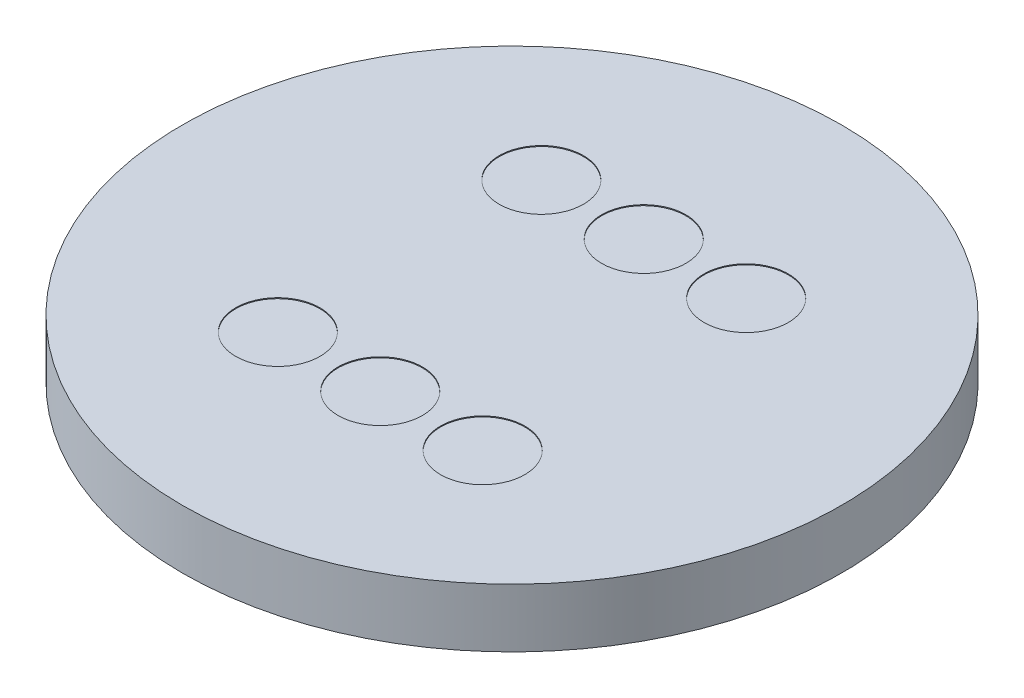
SolidWorks part; units mm, degrees
ref_plane "Front Plane" through (0, 0, 0) normal (0, 0, 1) x (1, 0, 0)
ref_plane "Top Plane" through (0, 0, 0) normal (0, 1, 0) x (1, 0, 0)
ref_plane "Right Plane" through (0, 0, 0) normal (1, 0, 0) x (0, 0, -1)
sketch "Sketch2" plane through (0, 0, 0) normal (0, 1, 0) x (1, 0, 0)
  circle A0 centre (0, 0) radius 9.271
  circle A1 centre (0, 0) radius 7.874
  circle A2 centre (0, 0) radius 5.1435
  circle A3 centre (0, 0) radius 4.826
  circle A4 centre (0, 0) radius 2.159
  circle A5 centre (0, 0) radius 1.905
  dimension "D1" = 18.542
  dimension "D2" = 15.748
  dimension "D3" = 10.287
  dimension "D4" = 9.652
  dimension "D5" = 4.318
  dimension "D6" = 3.81
extrude "Boss-Extrude1" add sketch "Sketch2" along normal blind 1.651 contours A0
extrude "Cut-Extrude1" cut sketch "Sketch2<3>" along normal blind 0.0254 contours A1 A2 | A3 A4 | A5 region at (-7.6513, 0, 0) region at (-4.6895, 0, 0) region at (0, 0, 0)
sketch "Sketch2<3>" plane through (0, 0, 0) normal (0, 1, 0) x (1, 0, 0) same geometry as "Sketch2"
sketch "Sketch3" plane through (0, 1.651, 0) normal (0, 1, 0) x (1, 0, 0)
  line L0 (2.8811, -3.7064) -> (-2.8811, -3.7064) construction
  line L1 (2.8811, 3.7064) -> (-2.8811, 3.7064) construction
  line L2 (0, -3.7064) -> (0, 3.7064) construction
  circle A0 centre (-2.8811, 3.7064) radius 1.186
  circle A1 centre (0, 0) radius 9.271
  circle A2 centre (0, 0) radius 9.271
  circle A3 centre (0, 3.7064) radius 1.186
  circle A4 centre (2.8811, 3.7064) radius 1.186
  circle A5 centre (0, -3.7064) radius 1.186
  circle A6 centre (2.8811, -3.7064) radius 1.186
  circle A7 centre (-2.8811, -3.7064) radius 1.186
  point P7 (0, -4.837)
  point P9 (0, -3.7064)
  point P19 (0, -3.7064)
  point P21 (0, 3.7064)
  point P23 (0, 0)
  dimension "D1" = 0
extrude "Cut-Extrude2" cut sketch "Sketch3" against normal blind 0.0254 contours A0 | A3 | A4 | A5 | A7 | A6 region at (-2.8811, 1.651, -3.7064) region at (0, 1.651, -3.7064) region at (2.8811, 1.651, -3.7064) region at (0, 1.651, 3.7064) region at (-2.8811, 1.651, 3.7064)
